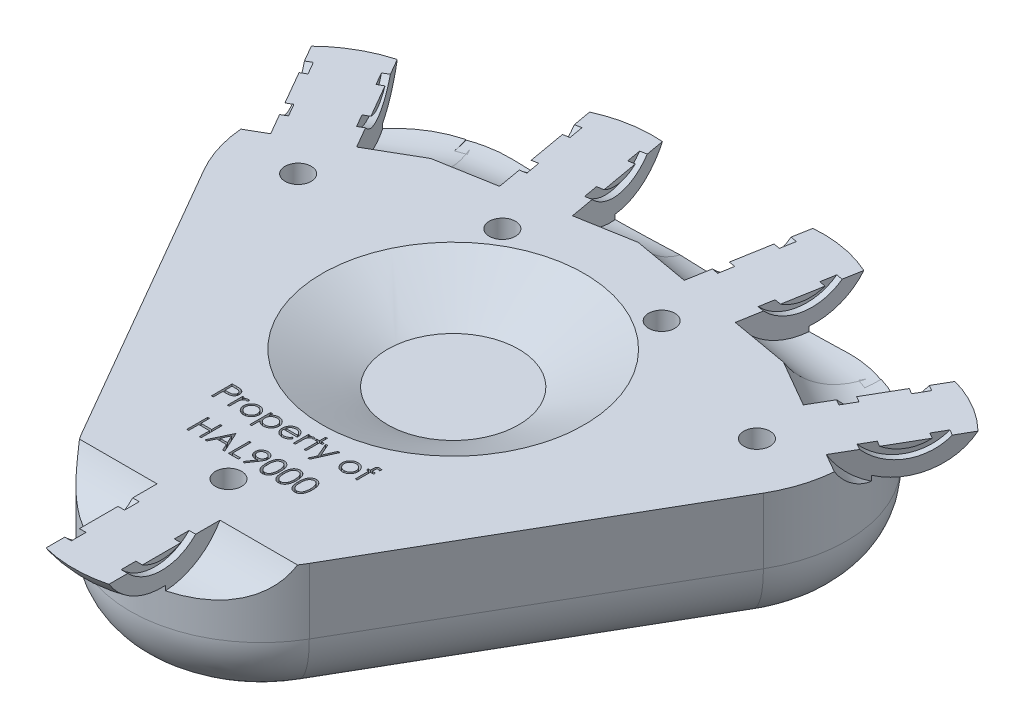
SolidWorks part; units mm, degrees
ref_plane "Front Plane" through (0, 0, 0) normal (0, 0, 1) x (1, 0, 0)
ref_plane "Top Plane" through (0, 0, 0) normal (0, 1, 0) x (1, 0, 0)
ref_plane "Right Plane" through (0, 0, 0) normal (1, 0, 0) x (0, 0, -1)
sketch "Sketch1" plane through (0, 0, 0) normal (0, 1, 0) x (1, 0, 0)
  line L0 (34.641, 0) -> (85.359, 0)
  line L1 (17.3205, -30) -> (42.6795, -73.923)
  line L3 (77.3205, -73.923) -> (102.6795, -30)
  arc A0 (77.3205, -73.923) -> (42.6795, -73.923) centre (60, -63.923) cw
  arc A1 (102.6795, -30) -> (85.359, 0) centre (85.359, -20) ccw
  arc A2 (34.641, 0) -> (17.3205, -30) centre (34.641, -20) ccw
  point P10 (120, 0)
  point P13 (0, 0)
  dimension "D3" = 20
  dimension "D1" = 120
  dimension "D2" = 60
  dimension "D4" = 60
extrude "Boss-Extrude1" add sketch "Sketch1" along normal blind 20
fillet "Fillet1" radius 10 6 edges at (30, 0, 51.9615) (17.3205, 0, 10) (60, 0, 0) (102.6795, 0, 10) (90, 0, 51.9615) (60, 0, 83.923)
ref_plane "Plane1" through (0, 15, 0) normal (0, 1, 0) x (1, 0, 0)
sketch "Sketch2" plane through (0, 20, 0) normal (0, 1, 0) x (1, 0, 0)
  line L0 (17.3205, -10) -> (90, -51.9615) construction
  line L1 (77.3205, -73.923) -> (102.6795, -30) construction
  line L2 (102.6795, -10) -> (30, -51.9615) construction
  line L3 (17.3205, -30) -> (42.6795, -73.923) construction
  circle A0 centre (60, -34.641) radius 20
  arc A1 (34.641, 0) -> (17.3205, -30) centre (34.641, -20) ccw construction
  arc A2 (102.6795, -30) -> (85.359, 0) centre (85.359, -20) ccw construction
sketch "Sketch3" plane through (0, 15, 0) normal (0, 1, 0) x (1, 0, 0)
  line L2 (17.3205, -10) -> (90, -51.9615) construction
  line L3 (77.3205, -73.923) -> (102.6795, -30) construction
  line L4 (102.6795, -10) -> (30, -51.9615) construction
  line L5 (17.3205, -30) -> (42.6795, -73.923) construction
  circle A0 centre (60, -34.641) radius 10
  arc A3 (34.641, 0) -> (17.3205, -30) centre (34.641, -20) ccw construction
  arc A4 (102.6795, -30) -> (85.359, 0) centre (85.359, -20) ccw construction
loft "Cut-Loft1" cut profiles "Sketch3", "Sketch2" connector at (50.0727, 15, 33.4376) connector at (41.9573, 20, 26.0119)
sketch "Sketch4" plane through (0, 20, 0) normal (0, 1, 0) x (1, 0, 0)
  line L0 (60, -83.923) -> (17.3205, -10) construction
  line L2 (74.7979, 0) -> (84.9493, -1.79) construction
  line L3 (60, -83.923) -> (102.6795, -10) construction
  line L4 (60, -83.923) -> (45.2021, 0) construction
  line L6 (60, -83.923) -> (74.7979, 0) construction
  line L7 (85.359, 0) -> (34.641, 0) construction
  line L9 (45.2021, 0) -> (50.8111, 0.989) construction
  line L12 (17.3205, -10) -> (22.8665, -6.798) construction
  line L14 (102.6795, -10) -> (106.9888, -12.488) construction
  line L15 (60, -83.923) -> (60, -68.923) construction
  line L16 (60, -83.923) -> (70.4731, -83.923) construction
  arc A0 (34.641, 0) -> (17.3205, -30) centre (34.641, -20) ccw construction
  arc A2 (42.6795, -73.923) -> (77.3205, -73.923) centre (60, -63.923) ccw construction
  circle A6 centre (60, -83.923) radius 85.2177
  circle A7 centre (60, -83.923) radius 70
  dimension "D1" = 20
  dimension "D2" = 20
  dimension "D3" = 60
ref_plane "Plane3" through (43.8391, 0, -7.73) normal (0.9848, 0, -0.1736) x (-0.1736, 0, -0.9848)
ref_plane "Plane4" through (72.5425, 0, 12.7912) normal (0.9848, 0, 0.1736) x (0.1736, 0, -0.9848)
ref_plane "Plane5" through (8.6603, 0, -5) normal (0.866, 0, -0.5) x (-0.5, 0, -0.866)
ref_plane "Plane6" through (81.3397, 0, 46.9615) normal (0.866, 0, 0.5) x (0.5, 0, -0.866)
ref_plane "Plane7" through (21.3397, 0, -36.9615) normal (0.5, 0, -0.866) x (-0.866, 0, -0.5)
ref_plane "Plane8" through (8.6603, 0, 15) normal (-0.5, 0, -0.866) x (-0.866, 0, 0.5)
ref_plane "Plane9" through (0, 0, 83.923) normal (0, 0, 1) x (1, 0, 0)
ref_plane "Plane14" through (0, 20, 0) normal (0, 1, 0) x (1, 0, 0)
sketch "Sketch5" plane through (21.3397, 0, 7.6795) normal (-0.5, 0, -0.866) x (-0.866, 0, 0.5)
  line L0 (4.641, 46.9474) -> (4.641, -46.9474) construction
  line L1 (-0.159, 25) -> (9.441, 25)
  line L2 (14.641, 20) -> (-15.359, 20) construction
  line L3 (9.441, 25) -> (9.441, 34.4742)
  line L4 (-0.159, 25) -> (-0.159, 34.4742)
  ellipse E0 centre (4.641, 25) end of major axis (19.641, 25) minor radius 10 (9.441, 34.4742) -> (-0.159, 34.4742) ccw
  dimension "D1" = 5
  dimension "D2" = 4.8
  dimension "D3" = 4.8
revolve "Revolve1" add sketch "Sketch5" angle 360 about L1
ref_plane "Plane10" through (1.363, 0, 7.73) normal (-0.1736, 0, -0.9848) x (-0.9848, 0, 0.1736)
ref_plane "Plane11" through (2.2554, 0, -12.7912) normal (0.1736, 0, -0.9848) x (-0.9848, 0, -0.1736)
sketch "Sketch6" plane through (8.6603, 0, -5) normal (0.866, 0, -0.5) x (-0.5, 0, -0.866)
  circle A0 centre (-17.3205, 25) radius 5
  arc A1 (-17.3206, 15) -> (-25.9807, 20) centre (-17.3205, 25) ccw construction
  dimension "D1" = 0
extrude "Cut-Extrude1" cut sketch "Sketch6" against normal blind 15 and the other way blind 15
sketch "Sketch11" plane through (4.5033, 0, -2.6) normal (-0.866, 0, 0.5) x (0.5, 0, 0.866)
  circle A0 centre (17.3205, 25) radius 10.2
extrude "Cut-Extrude3" cut sketch "Sketch11" along normal blind 10
sketch "Sketch12" plane through (12.8172, 0, -7.4) normal (0.866, 0, -0.5) x (-0.5, 0, -0.866)
  circle A0 centre (-17.3205, 25) radius 10.2
extrude "Cut-Extrude4" cut sketch "Sketch12" along normal blind 10
sketch "Sketch13" plane through (4.5033, 0, -2.6) normal (-0.866, 0, 0.5) x (0.5, 0, 0.866)
  circle A0 centre (17.3205, 25) radius 5.8
  circle A1 centre (17.3205, 25) radius 7.2
  circle A2 centre (17.3205, 25) radius 5 construction
  dimension "D1" = 0.8
  dimension "D2" = 1.4
extrude "Cut-Extrude5" cut sketch "Sketch13" against normal blind 1
sketch "Sketch14" plane through (12.8172, 0, -7.4) normal (0.866, 0, -0.5) x (-0.5, 0, -0.866)
  circle A0 centre (-17.3205, 25) radius 5.8
  circle A1 centre (-17.3205, 25) radius 7.2
  circle A2 centre (-17.3205, 25) radius 5 construction
  dimension "D1" = 0.8
  dimension "D2" = 1.4
extrude "Cut-Extrude6" cut sketch "Sketch14" against normal blind 1
ref_plane "Plane13" through (60, 0, 0) normal (1, 0, 0) x (0, 0, -1)
sketch "Sketch17" plane through (1.363, 0, 7.73) normal (-0.1736, 0, -0.9848) x (-0.9848, 0, 0.1736)
  line L0 (-44.5154, 46.8697) -> (-44.5154, -46.8697) construction
  line L1 (-49.3154, 25) -> (-39.7154, 25)
  line L2 (93.7395, 20) -> (-93.7395, 20) construction
  line L3 (-49.3154, 25) -> (-49.3154, 34.4742)
  line L4 (-39.7154, 25) -> (-39.7154, 34.4742)
  ellipse E0 centre (-44.5154, 25) end of major axis (-29.5154, 25) minor radius 10 (-39.7154, 34.4742) -> (-49.3154, 34.4742) ccw
  dimension "D1" = 5
  dimension "D2" = 4.8
  dimension "D3" = 4.8
revolve "Revolve3" add sketch "Sketch17" angle 360 about L1
sketch "Sketch18" plane through (39.112, 0, -6.8965) normal (-0.9848, 0, 0.1736) x (0.1736, 0, 0.9848)
  circle A0 centre (7.8493, 25) radius 5
extrude "Cut-Extrude7" cut sketch "Sketch18" against normal blind 10
sketch "Sketch19" plane through (48.5662, 0, -8.5635) normal (0.9848, 0, -0.1736) x (-0.1736, 0, -0.9848)
  circle A0 centre (-7.8493, 25) radius 10.2
extrude "Cut-Extrude8" cut sketch "Sketch19" along normal blind 10
sketch "Sketch20" plane through (39.112, 0, -6.8965) normal (-0.9848, 0, 0.1736) x (0.1736, 0, 0.9848)
  line L0 (7.8493, 3.1326) -> (7.8493, -3.1326) construction
  circle A0 centre (7.8493, 25) radius 10.2
extrude "Cut-Extrude9" cut sketch "Sketch20" along normal blind 12
sketch "Sketch21" plane through (2.2554, 0, -12.7912) normal (0.1736, 0, -0.9848) x (-0.9848, 0, -0.1736)
  line L0 (-73.6615, 46.8697) -> (-73.6615, -46.8697) construction
  line L1 (-78.4615, 25) -> (-68.8615, 25)
  line L2 (-73.6615, 20) -> (-83.9756, 20) construction
  line L3 (-78.4615, 25) -> (-78.4615, 34.4742)
  line L4 (-68.8615, 25) -> (-68.8615, 34.4742)
  ellipse E0 centre (-73.6615, 25) end of major axis (-58.6615, 25) minor radius 10 (-68.8615, 34.4742) -> (-78.4615, 34.4742) ccw
  dimension "D1" = 5
  dimension "D2" = 4.8
  dimension "D3" = 4.8
revolve "Revolve4" add sketch "Sketch21" angle 360 about L1
sketch "Sketch22" plane through (72.5425, 0, 12.7912) normal (0.9848, 0, 0.1736) x (0.1736, 0, -0.9848)
  line L0 (12.9885, -5.6694) -> (12.9885, 5.6694) construction
  circle A0 centre (12.9885, 25) radius 5
extrude "Cut-Extrude10" cut sketch "Sketch22" against normal blind 10 and the other way blind 10
sketch "Sketch23" plane through (77.2695, 0, 13.6247) normal (0.9848, 0, 0.1736) x (0.1736, 0, -0.9848)
  circle A0 centre (12.9885, 25) radius 5.8
  circle A1 centre (12.9885, 25) radius 7.2
  circle A2 centre (12.9885, 25) radius 5 construction
  dimension "D1" = 0.8
  dimension "D2" = 1.4
extrude "Cut-Extrude11" cut sketch "Sketch23" against normal blind 1
sketch "Sketch24" plane through (67.8154, 0, 11.9577) normal (-0.9848, 0, -0.1736) x (-0.1736, 0, 0.9848)
  line L0 (-12.9885, 5.6694) -> (-12.9885, -5.6694) construction
  circle A0 centre (-12.9885, 25) radius 7.2
  circle A1 centre (-12.9885, 25) radius 5.8
  circle A2 centre (-12.9885, 25) radius 5 construction
  dimension "D1" = 0.8
  dimension "D2" = 1.4
extrude "Cut-Extrude12" cut sketch "Sketch24" against normal blind 1
sketch "Sketch25" plane through (77.2695, 0, 13.6247) normal (0.9848, 0, 0.1736) x (0.1736, 0, -0.9848)
  circle A0 centre (12.9885, 25) radius 10.2
extrude "Cut-Extrude13" cut sketch "Sketch25" along normal blind 12
sketch "Sketch26" plane through (67.8154, 0, 11.9577) normal (-0.9848, 0, -0.1736) x (-0.1736, 0, 0.9848)
  circle A0 centre (-12.9885, 25) radius 10.2
extrude "Cut-Extrude14" cut sketch "Sketch26" along normal blind 12
sketch "Sketch27" plane through (48.5662, 0, -8.5635) normal (0.9848, 0, -0.1736) x (-0.1736, 0, -0.9848)
  line L0 (-7.8493, -3.1326) -> (-7.8493, 3.1326) construction
  circle A0 centre (-7.8493, 25) radius 7.2
  circle A1 centre (-7.8493, 25) radius 5.8
  circle A2 centre (-7.8493, 25) radius 5 construction
  dimension "D1" = 0.8
  dimension "D2" = 1.4
extrude "Cut-Extrude15" cut sketch "Sketch27" against normal blind 1
sketch "Sketch28" plane through (39.112, 0, -6.8965) normal (-0.9848, 0, 0.1736) x (0.1736, 0, 0.9848)
  circle A0 centre (7.8493, 25) radius 7.2
  circle A1 centre (7.8493, 25) radius 5.8
  circle A2 centre (7.8493, 25) radius 5 construction
  dimension "D1" = 0.8
  dimension "D2" = 1.4
extrude "Cut-Extrude16" cut sketch "Sketch28" against normal blind 1
sketch "Sketch29" plane through (21.3397, 0, -36.9615) normal (0.5, 0, -0.866) x (-0.866, 0, -0.5)
  line L0 (-93.923, 46.9474) -> (-93.923, -46.9474) construction
  line L1 (-98.723, 25) -> (-89.123, 25)
  line L2 (-98.723, 25) -> (-98.723, 34.4742)
  line L3 (-89.123, 25) -> (-89.123, 34.4742)
  line L4 (-79.9062, 20) -> (-103.923, 20) construction
  ellipse E0 centre (-93.923, 25) end of major axis (-78.923, 25) minor radius 10 (-89.123, 34.4742) -> (-98.723, 34.4742) ccw
  dimension "D1" = 5
  dimension "D2" = 4.8
  dimension "D3" = 4.8
revolve "Revolve5" add sketch "Sketch29" angle 360 about L1
sketch "Sketch31" plane through (85.4967, 0, 49.3615) normal (0.866, 0, 0.5) x (0.5, 0, -0.866)
  line L0 (42.6795, -2.7368) -> (42.6795, 2.7368) construction
  circle A1 centre (42.6795, 25) radius 7.2
  circle A2 centre (42.6795, 25) radius 5.8
  dimension "D1" = 11.6
  dimension "D2" = 1.4
extrude "Cut-Extrude17" cut sketch "Sketch31" against normal blind 1
sketch "Sketch32" plane through (81.3397, 0, 46.9615) normal (0.866, 0, 0.5) x (0.5, 0, -0.866)
  circle A1 centre (42.6795, 25) radius 5
extrude "Cut-Extrude18" cut sketch "Sketch32" against normal blind 10 and the other way blind 10
sketch "Sketch33" plane through (77.1828, 0, 44.5615) normal (-0.866, 0, -0.5) x (-0.5, 0, 0.866)
  line L0 (-42.6795, 2.7368) -> (-42.6795, -2.7368) construction
  circle A0 centre (-42.6795, 25) radius 7.2
  circle A1 centre (-42.6795, 25) radius 5.8
  circle A2 centre (-42.6795, 25) radius 5 construction
  dimension "D1" = 0.8
  dimension "D2" = 1.4
extrude "Cut-Extrude19" cut sketch "Sketch33" against normal blind 1
sketch "Sketch34" plane through (0, 0, 83.923) normal (0, 0, 1) x (1, 0, 0)
  line L0 (60, -42.8798) -> (60, 42.8798) construction
  line L1 (55.2, 25) -> (64.8, 25)
  line L2 (55.2, 25) -> (55.2, 34.4742)
  line L3 (64.8, 25) -> (64.8, 34.4742)
  line L4 (60, 20) -> (70.4731, 20) construction
  ellipse E0 centre (60, 25) end of major axis (75, 25) minor radius 10 (64.8, 34.4742) -> (55.2, 34.4742) ccw
  dimension "D1" = 5
  dimension "D2" = 4.8
  dimension "D3" = 4.8
revolve "Revolve6" add sketch "Sketch34" angle 360 about L1
sketch "Sketch35" plane through (85.4967, 0, 49.3615) normal (0.866, 0, 0.5) x (0.5, 0, -0.866)
  circle A0 centre (42.6795, 25) radius 10.2
extrude "Cut-Extrude20" cut sketch "Sketch35" along normal blind 10
sketch "Sketch36" plane through (77.1828, 0, 44.5615) normal (-0.866, 0, -0.5) x (-0.5, 0, 0.866)
  circle A0 centre (-42.6795, 25) radius 10.2
extrude "Cut-Extrude21" cut sketch "Sketch36" along normal blind 10
sketch "Sketch37" plane through (60, 0, 0) normal (1, 0, 0) x (0, 0, -1)
  line L0 (-83.923, 42.8798) -> (-83.923, -42.8798) construction
  circle A0 centre (-83.923, 25) radius 5
extrude "Cut-Extrude22" cut sketch "Sketch37" against normal blind 10 and the other way blind 10
sketch "Sketch38" plane through (64.8, 0, 0) normal (1, 0, 0) x (0, 0, -1)
  circle A0 centre (-83.923, 25) radius 5.8
  circle A1 centre (-83.923, 25) radius 7.2
  circle A2 centre (-83.923, 25) radius 5 construction
  dimension "D1" = 0.8
  dimension "D2" = 1.4
extrude "Cut-Extrude23" cut sketch "Sketch38" against normal blind 1
sketch "Sketch39" plane through (55.2, 0, 0) normal (-1, 0, 0) x (0, 0, 1)
  circle A0 centre (83.923, 25) radius 5.8
  circle A1 centre (83.923, 25) radius 7.2
  circle A2 centre (83.923, 25) radius 5 construction
  dimension "D1" = 0.8
  dimension "D2" = 1.4
extrude "Cut-Extrude24" cut sketch "Sketch39" against normal blind 1
sketch "Sketch40" plane through (55.2, 0, 0) normal (-1, 0, 0) x (0, 0, 1)
  circle A0 centre (83.923, 25) radius 10.2
extrude "Cut-Extrude25" cut sketch "Sketch40" along normal blind 20
sketch "Sketch41" plane through (64.8, 0, 0) normal (1, 0, 0) x (0, 0, -1)
  circle A0 centre (-83.923, 25) radius 10.2
extrude "Cut-Extrude26" cut sketch "Sketch41" along normal blind 20
sketch "Sketch44" plane through (0, 20, 0) normal (0, 1, 0) x (1, 0, 0)
  line L0 (60, -83.923) -> (17.3205, -10) construction
  line L1 (60, -83.923) -> (45.2021, 0) construction
  line L2 (60, -83.923) -> (74.7979, 0) construction
  line L3 (60, -83.923) -> (102.6795, -10) construction
  circle A0 centre (25, -23.3013) radius 2
  circle A1 centre (60, -83.923) radius 70 construction
  circle A2 centre (47.8446, -14.9865) radius 2
  circle A3 centre (72.1554, -14.9865) radius 2
  circle A4 centre (95, -23.3013) radius 2
  circle A5 centre (60, -68.923) radius 2
extrude "Cut-Extrude27" cut sketch "Sketch44" against normal blind 20
sketch "Sketch45" plane through (0, 0, 0) normal (0, 1, 0) x (1, 0, 0)
  line L0 (45.1897, -59.2643) -> (72.7011, -59.2643) construction
  text T0 "Property of\r\nHAL9000"
extrude "Cut-Extrude28" cut sketch "Sketch45" against normal blind 3 from surface starting at face at (25, 20, 25.3013)
sketch "Sketch47" plane through (0, 0, 0) normal (0, 1, 0) x (1, 0, 0)
  line L0 (102.6795, -30) -> (77.3205, -73.923)
  line L1 (102.6795, -30) -> (77.3205, -73.923)
  line L2 (64.8, -83.3385) -> (64.8, -93.3972)
  line L3 (64.8, -83.3385) -> (64.8, -93.3972)
  line L4 (55.2, -93.3961) -> (55.2, -83.3385)
  line L5 (55.2, -93.3961) -> (55.2, -83.3385)
  line L6 (42.6795, -73.923) -> (17.3205, -30)
  line L7 (42.6795, -73.923) -> (17.3205, -30)
  line L8 (15.0978, -15.7501) -> (8.4265, -4.1951)
  line L9 (15.0978, -15.7501) -> (8.4265, -4.1951)
  line L10 (16.741, 0.6037) -> (20.4816, -5.8752)
  line L11 (16.741, 0.6037) -> (20.4816, -5.8752)
  line L12 (34.641, 0) -> (40.3281, 0)
  line L13 (34.641, 0) -> (40.3281, 0)
  line L14 (40.3281, 0) -> (38.8299, 8.4967)
  line L15 (40.3281, 0) -> (38.8299, 8.4967)
  line L16 (48.284, 10.1637) -> (50.0761, 0)
  line L17 (48.284, 10.1637) -> (50.0761, 0)
  line L18 (50.0761, 0) -> (69.9239, 0)
  line L19 (50.0761, 0) -> (69.9239, 0)
  line L20 (69.9239, 0) -> (71.716, 10.1638)
  line L21 (69.9239, 0) -> (71.716, 10.1638)
  line L22 (81.1701, 8.4967) -> (79.6719, 0)
  line L23 (81.1701, 8.4967) -> (79.6719, 0)
  line L24 (79.6719, 0) -> (85.359, 0)
  line L25 (79.6719, 0) -> (85.359, 0)
  line L26 (99.5184, -5.8752) -> (103.2597, 0.6049)
  line L27 (99.5184, -5.8752) -> (103.2597, 0.6049)
  line L28 (111.5728, -4.1963) -> (104.9022, -15.7501)
  line L29 (111.5728, -4.1963) -> (104.9022, -15.7501)
  arc A0 (102.6795, -30) -> (104.9022, -15.7501) centre (85.359, -20) ccw
  arc A1 (102.6795, -30) -> (104.9022, -15.7501) centre (85.359, -20) ccw
  arc A2 (64.8, -83.3385) -> (77.3205, -73.923) centre (60, -63.923) ccw
  arc A3 (64.8, -83.3385) -> (77.3205, -73.923) centre (60, -63.923) ccw
  arc A4 (42.6795, -73.923) -> (55.2, -83.3385) centre (60, -63.923) ccw
  arc A5 (42.6795, -73.923) -> (55.2, -83.3385) centre (60, -63.923) ccw
  arc A6 (15.0978, -15.7501) -> (17.3205, -30) centre (34.641, -20) ccw
  arc A7 (15.0978, -15.7501) -> (17.3205, -30) centre (34.641, -20) ccw
  arc A8 (34.641, 0) -> (20.4816, -5.8752) centre (34.641, -20) ccw
  arc A9 (34.641, 0) -> (20.4816, -5.8752) centre (34.641, -20) ccw
  arc A10 (99.5184, -5.8752) -> (85.359, 0) centre (85.359, -20) ccw
  arc A11 (99.5184, -5.8752) -> (85.359, 0) centre (85.359, -20) ccw
  spline S0 degree 3 poles (483.75, -2048.5841) (102.344, -62.7532) (85.1738, -89.6672) (63.6128, -93.6279) (63.0151, -93.72) (62.2149, -93.82) (61.2099, -93.9025) (60.2016, -93.9298) (58.79, -93.911) (57.5825, -93.813) (56.4866, -93.6442) (56.0896, -93.5742) (55.7926, -93.5176) (34.1972, -89.164) (15.4437, -70.329) (-379.7905, -2045.0813) knots -6.608894 -6.608894 -6.608894 -6.608894 0.062478 0.12498 0.187481 0.249983 0.374985 0.499988 0.56249 0.812496 0.874997 0.906248 0.937499 0.968749 7.735431 7.735431 7.735431 7.735431 only from (64.8, -93.3972) to (55.2, -93.3961)
  spline S1 degree 3 poles (64.8, -93.3972) (64.6026, -93.4379) (64.2075, -93.5187) (63.6128, -93.6279) (63.0151, -93.72) (62.2149, -93.82) (61.2099, -93.9025) (60.2016, -93.9298) (58.79, -93.911) (57.5825, -93.813) (56.4866, -93.6442) (56.0896, -93.5742) (55.7926, -93.5176) (55.4961, -93.4579) (55.2987, -93.4168) (55.2, -93.3961) knots 0 0 0 0 0.062478 0.12498 0.187481 0.249983 0.374985 0.499988 0.56249 0.812496 0.874997 0.906248 0.937499 0.968749 1 1 1 1
  spline S2 degree 3 poles (-1302.0832, 1505.9449) (-0.1413, -72.7814) (-10.5736, -19.4079) (9.8103, -3.0225) (10.4532, -2.5357) (11.2824, -1.9619) (12.3143, -1.3291) (13.3785, -0.7524) (14.2901, -0.3212) (15.0331, -0.0076) (15.5968, 0.2113) (38.3238, 8.295) (71.029, -12.3299) (-594.812, 1904.3165) knots -7.858994 -7.858994 -7.858994 -7.858994 0.124974 0.187475 0.249977 0.374981 0.499985 0.624989 0.749992 0.812494 0.874996 0.937498 8.291139 8.291139 8.291139 8.291139 only from (8.4265, -4.1951) to (16.741, 0.6037)
  spline S3 degree 3 poles (8.4265, -4.1951) (8.7273, -3.9266) (9.1819, -3.5276) (9.8103, -3.0225) (10.4532, -2.5357) (11.2824, -1.9619) (12.3143, -1.3291) (13.3785, -0.7524) (14.2901, -0.3212) (15.0331, -0.0076) (15.5968, 0.2113) (16.1666, 0.414) (16.5494, 0.541) (16.741, 0.6037) knots 0 0 0 0 0.124974 0.187475 0.249977 0.374981 0.499985 0.624989 0.749992 0.812494 0.874996 0.937498 1 1 1 1
  spline S4 degree 3 poles (-680.3696, 1874.1096) (7.4238, -51.152) (16.2198, 1.2352) (41.1069, 9.3116) (42.2776, 9.6174) (43.4637, 9.8587) (44.6609, 10.0376) (45.8657, 10.1513) (46.8731, 10.1884) (71.6675, 10.0039) (95.8026, -22.5193) (123.8751, 2008.1639) knots -7.736162 -7.736162 -7.736162 -7.736162 0.124999 0.249999 0.374999 0.499999 0.625 0.75 0.875 0.9375 8.437722 8.437722 8.437722 8.437722 only from (38.8299, 8.4967) to (48.284, 10.1637)
  spline S5 degree 3 poles (38.8299, 8.4967) (39.2046, 8.6457) (39.9563, 8.9382) (41.1069, 9.3116) (42.2776, 9.6174) (43.4637, 9.8587) (44.6609, 10.0376) (45.8657, 10.1513) (46.8731, 10.1884) (47.6794, 10.1824) (48.0825, 10.1706) (48.284, 10.1637) knots 0 0 0 0 0.124999 0.249999 0.374999 0.499999 0.625 0.75 0.875 0.9375 1 1 1 1
  spline S6 degree 3 poles (33.9668, 2009.2471) (21.8029, -35.1462) (47.986, 11.0733) (74.1344, 10.1507) (75.3391, 10.0376) (76.5362, 9.8587) (77.7224, 9.6174) (78.8934, 9.3122) (79.8528, 9.0025) (103.0887, 0.3489) (114.6447, -38.4676) (835.5588, 1860.149) knots -7.736162 -7.736162 -7.736162 -7.736162 0.124999 0.249999 0.374999 0.499999 0.625 0.75 0.875 0.9375 8.437722 8.437722 8.437722 8.437722 only from (71.716, 10.1638) to (81.1701, 8.4967)
  spline S7 degree 3 poles (71.716, 10.1638) (72.1191, 10.1756) (72.9255, 10.1933) (74.1344, 10.1507) (75.3391, 10.0376) (76.5362, 9.8587) (77.7224, 9.6174) (78.8934, 9.3122) (79.8528, 9.0025) (80.6084, 8.7211) (80.9831, 8.5721) (81.1701, 8.4967) knots 0 0 0 0 0.124999 0.249999 0.374999 0.499999 0.625 0.75 0.875 0.9375 1 1 1 1
  spline S8 degree 3 poles (755.8228, 1890.6052) (39.5784, -26.2683) (80.5849, 9.453) (104.9671, -0.0072) (105.7101, -0.3206) (106.6216, -0.7518) (107.6856, -1.329) (108.7172, -1.9624) (109.5464, -2.5362) (110.1894, -3.0229) (110.6609, -3.4015) (129.0249, -19.0417) (127.5159, -57.6775) (1454.4586, 1477.2772) knots -7.858988 -7.858988 -7.858988 -7.858988 0.124974 0.187475 0.249977 0.374981 0.499985 0.624989 0.749992 0.812494 0.874996 0.937498 8.291084 8.291084 8.291084 8.291084 only from (103.2597, 0.6049) to (111.5728, -4.1963)
  spline S9 degree 3 poles (103.2597, 0.6049) (103.6426, 0.4786) (104.2154, 0.2844) (104.9671, -0.0072) (105.7101, -0.3206) (106.6216, -0.7518) (107.6856, -1.329) (108.7172, -1.9624) (109.5464, -2.5362) (110.1894, -3.0229) (110.6609, -3.4015) (111.1213, -3.7937) (111.4227, -4.0617) (111.5728, -4.1963) knots 0 0 0 0 0.124974 0.187475 0.249977 0.374981 0.499985 0.624989 0.749992 0.812494 0.874996 0.937498 1 1 1 1
ref_axis "Axis1" through (19.399, 25, 8.8) along (-0.866, 0, 0.5)
ref_axis "Axis2" through (49.6441, 25, -0.7832) along (-0.9848, 0, 0.1736)
ref_axis "Axis3" through (81.2091, 25, 1.1305) along (-0.9848, 0, -0.1736)
ref_axis "Axis4" through (110.5864, 25, 14.5651) along (-0.866, 0, -0.5)
ref_axis "Axis5" through (64.8, 25, 83.923) along (-1, 0, 0)
ref_plane "Plane15" through (8.6603, 0, -5) normal (-0.866, 0, 0.5) x (0.5, 0, 0.866)
ref_plane "Plane16" through (43.8391, 0, -7.73) normal (-0.9848, 0, 0.1736) x (0.1736, 0, 0.9848)
ref_plane "Plane17" through (72.5425, 0, 12.7912) normal (0.9848, 0, 0.1736) x (0.1736, 0, -0.9848)
ref_plane "Plane18" through (81.3397, 0, 46.9615) normal (-0.866, 0, -0.5) x (-0.5, 0, 0.866)
ref_plane "Plane19" through (60, 0, 0) normal (1, 0, 0) x (0, 0, -1)
sketch "Sketch48" plane through (0, 0, 0) normal (0, 1, 0) x (1, 0, 0)
  line L0 (60, -34.641) -> (17.3205, -10)
  line L1 (19.399, -8.8) -> (15.242, -11.2) construction
  line L2 (3.2499, 14.3711) -> (14.0707, -4.3711) construction
  line L3 (45.2021, 0) -> (60, -34.641)
  line L4 (-20.5475, 0) -> (20.5475, 0) construction
  line L5 (41.9601, 18.3864) -> (45.7181, -2.9264) construction
  line L6 (60, -34.641) -> (74.7979, 0)
  line L7 (81.2091, -1.1305) -> (68.3867, 1.1305) construction
  line L8 (60, -34.641) -> (102.6795, -10)
  line L9 (86.7501, -37.5904) -> (75.9293, -56.3326) construction
  line L10 (60, -83.923) -> (60, -34.641)
  line L11 (60, -10.4216) -> (60, 10.4216) construction
  line L12 (64.8, -83.923) -> (55.2, -83.923) construction
  line L13 (110.5864, -14.5651) -> (94.7726, -5.4349) construction
  line L14 (95.1941, -86.3911) -> (95.1941, -15.9878) construction
  line L15 (17.3205, -10) -> (60, -85.1281)
  line L16 (60, -85.1281) -> (45.2021, 0)
  line L17 (60, -85.1281) -> (74.7979, 0)
  line L18 (60, -85.1281) -> (102.6795, -10)
  line L19 (49.6441, 0.7832) -> (40.7601, -0.7832) construction
  line L20 (0, 0) -> (60, -34.641)
  circle A2 centre (60, -34.641) radius 20
  circle A3 centre (60, -34.641) radius 20
  dimension "D2" = 60
  dimension "D3" = 23.131
  dimension "D4" = 23.131
  dimension "D5" = 60
  dimension "D6" = 49.282
  dimension "D7" = 49.282
  dimension "D8" = 86.4047
  dimension "D9" = 86.4047
  dimension "D10" = 86.4047
  dimension "D11" = 86.4047
  dimension "D12" = 29.6
  dimension "D13" = 37.6693
  dimension "D14" = 37.6693
  dimension "D15" = 49.282
  dimension "D16" = 34.641
  dimension "D17" = 60
  dimension "D1" = 10
sketch "Sketch49" plane through (8.6603, 0, -5) normal (-0.866, 0, 0.5) x (0.5, 0, 0.866)
  line L0 (17.3205, 25) -> (30.6795, 20)
  line L1 (34.6795, 20) -> (30.6795, 20) construction
  dimension "D1" = 5
  dimension "D2" = 13.359
sketch "Sketch50" plane through (0, 0, 0) normal (0, 1, 0) x (1, 0, 0)
  line L0 (17.3205, -10) -> (60, -83.923)
  line L1 (19.399, -8.8) -> (15.242, -11.2) construction
  line L2 (60, -83.923) -> (45.2021, 0)
  line L3 (49.6441, 0.7832) -> (40.7601, -0.7832) construction
  line L4 (60, -83.923) -> (74.7979, 0)
  line L5 (81.2091, -1.1305) -> (68.3867, 1.1305) construction
  line L6 (60, -83.923) -> (102.6795, -10)
  line L7 (110.5864, -14.5651) -> (94.7726, -5.4349) construction
  line L8 (3.2499, 14.3711) -> (14.0707, -4.3711) construction
  line L9 (41.9601, 18.3864) -> (45.7181, -2.9264) construction
  line L10 (70.6635, -23.4476) -> (74.4215, -2.1348) construction
  line L11 (86.7501, -37.5904) -> (75.9293, -56.3326) construction
  line L14 (60, -34.641) -> (60, 9.2816) construction
  circle A0 centre (60, -34.641) radius 10 construction
  point P26 (60, -34.641)
  dimension "D1" = 42.6795
  dimension "D2" = 24.641
  dimension "D3" = 34.641
  dimension "D4" = 14.7979
  dimension "D5" = 30
  dimension "D6" = 10
sketch "Sketch51" plane through (0, 20, 0) normal (0, 1, 0) x (1, 0, 0)
  line L1 (-8.7621, 18.2108) -> (130.3386, 18.2108)
  line L2 (-8.7621, 18.2108) -> (-8.7621, -102.2787)
  line L3 (-8.7621, -102.2787) -> (130.3386, -102.2787)
  line L4 (130.3386, 18.2108) -> (130.3386, -102.2787)
extrude "Cut-Extrude29" cut sketch "Sketch51" along normal through all
sketch "Sketch52" plane through (0, 20, 0) normal (0, 1, 0) x (1, 0, 0)
  line L0 (-13.8137, 0) -> (13.8137, 0) construction
  line L1 (14.641, 0) -> (105.359, 0)
  line L2 (14.641, 0) -> (14.641, -83.923)
  line L3 (14.641, -83.923) -> (105.359, -83.923)
  line L4 (105.359, 0) -> (105.359, -83.923)
  line L5 (14.641, -83.923) -> (105.359, 0) construction
  line L6 (14.641, 0) -> (105.359, -83.923) construction
  arc A0 (42.6795, -73.923) -> (55.2, -83.3385) centre (60, -63.923) ccw construction
  arc A1 (15.0978, -15.7501) -> (17.3205, -30) centre (34.641, -20) ccw construction
  arc A2 (102.6795, -30) -> (104.9022, -15.7501) centre (85.359, -20) ccw construction
  dimension "D1" = 83.923
  dimension "D2" = 83.923
  dimension "D3" = 90.718
